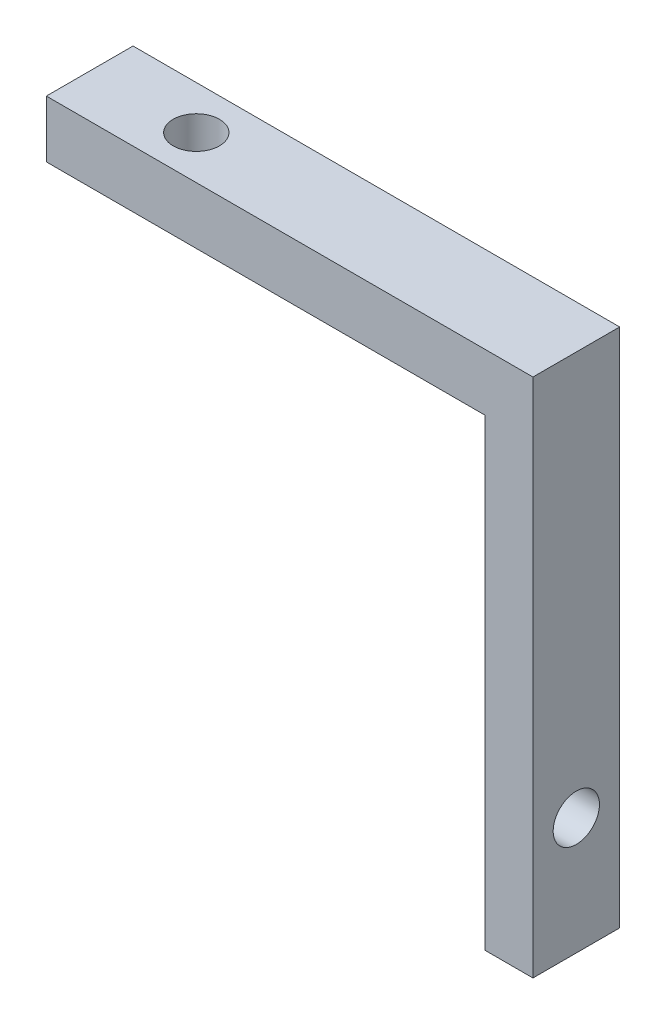
SolidWorks part; units mm, degrees
ref_plane "Front Plane" through (0, 0, 0) normal (0, 0, 1) x (1, 0, 0)
ref_plane "Top Plane" through (0, 0, 0) normal (0, 1, 0) x (1, 0, 0)
ref_plane "Right Plane" through (0, 0, 0) normal (1, 0, 0) x (0, 0, -1)
sketch "Sketch1" plane through (0, 0, 0) normal (0, 0, 1) x (1, 0, 0)
  line L0 (-7.3784, 23.9694) -> (22.9684, 23.9694)
  line L1 (22.9684, 23.9694) -> (22.9684, -8.1044)
  line L2 (-7.3784, 23.9694) -> (-7.3784, 27.9169)
  line L3 (-7.3784, 27.9169) -> (26.2991, 27.9169)
  line L4 (26.2991, 27.9169) -> (26.2991, -8.1044)
  line L5 (26.2991, -8.1044) -> (22.9684, -8.1044)
  circle A0 centre (0, 0) radius 15 construction
  circle A1 centre (0, 0) radius 20 construction
  dimension "D1" = 30
  dimension "D2" = 40
extrude "Boss-Extrude1" add sketch "Sketch1" along normal blind 3 and the other way blind 3
sketch "Sketch2" plane through (0, 0, 3) normal (0, 0, 1) x (1, 0, 0)
  circle A0 centre (0, 0) radius 20 construction
hole_wizard "M3 Clearance Hole1" positions "Sketch3" profile "Sketch4" hole size "M3" standard "ANSI Metric" end condition up to next
sketch "Sketch3" plane through (0, 27.9169, 0) normal (0, 1, 0) x (1, 0, 0)
  point P0 (0, 0)
sketch "Sketch4" plane through (0, 27.9169, 0) normal (1, 0, 0) x (0, 0, 1)
  line L0 (0, 0) -> (0, 3.9475)
  line L1 (0, 3.9475) -> (1.6, 3.9475)
  line L2 (1.6, 3.9475) -> (1.6, 0)
  line L5 (1.6, 0) -> (0, 0)
  line L11 (0, -6.35) -> (0, 107.95) construction
  dimension "Thru Hole Dia." = 3.2
  dimension "Thru Hole Depth" = 3.9475
hole_wizard "M3 Clearance Hole2" positions "Sketch5" profile "Sketch6" hole size "M3" standard "ANSI Metric" end condition up to next
sketch "Sketch5" plane through (26.2991, 0, 0) normal (1, 0, 0) x (0, 0, -1)
  point P0 (0, 0)
sketch "Sketch6" plane through (26.2991, 0, 0) normal (0, 1, 0) x (0, 0, -1)
  line L0 (0, 0) -> (0, 3.3307)
  line L1 (0, 3.3307) -> (1.6, 3.3307)
  line L2 (1.6, 3.3307) -> (1.6, 0)
  line L5 (1.6, 0) -> (0, 0)
  line L11 (0, -6.35) -> (0, 107.95) construction
  dimension "Thru Hole Dia." = 3.2
  dimension "Thru Hole Depth" = 3.3307
